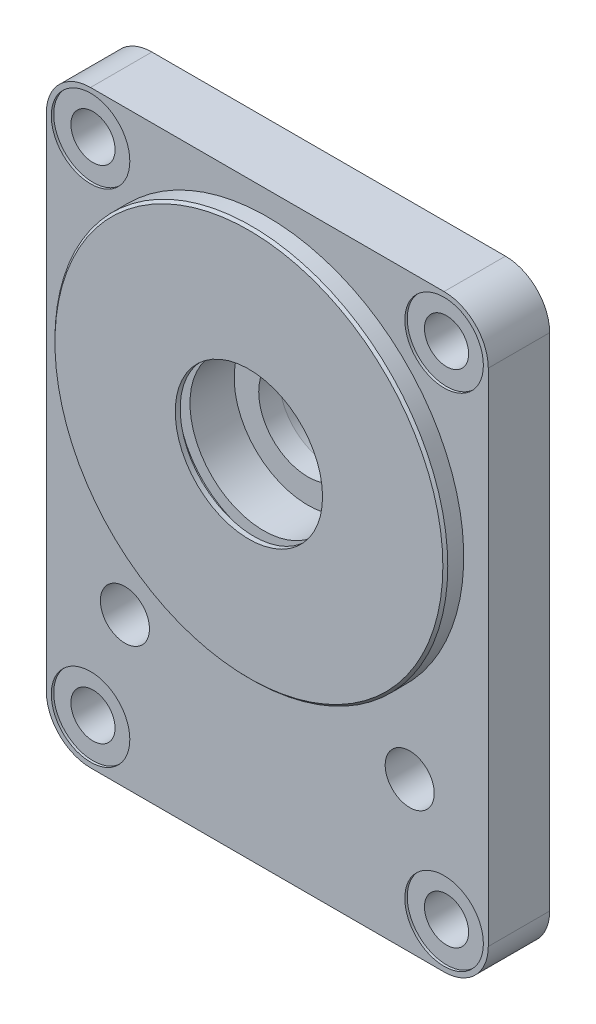
SolidWorks part; units mm, degrees
ref_plane "Front Plane" through (0, 0, 0) normal (0, 0, 1) x (1, 0, 0)
ref_plane "Top Plane" through (0, 0, 0) normal (0, 1, 0) x (1, 0, 0)
ref_plane "Right Plane" through (0, 0, 0) normal (1, 0, 0) x (0, 0, -1)
sketch "Sketch1" plane through (0, 0, 0) normal (0, 0, 1) x (1, 0, 0)
  line L1 (-36, -60) -> (36, -60)
  line L2 (-45, -51) -> (-45, 51)
  line L3 (-36, 60) -> (36, 60)
  line L4 (45, -51) -> (45, 51)
  line L6 (-45, 60) -> (-43.8588, 58.4785) construction
  arc A0 (-36, -60) -> (-45, -51) centre (-36, -51) cw
  arc A1 (36, -60) -> (45, -51) centre (36, -51) ccw
  arc A2 (36, 60) -> (45, 51) centre (36, 51) cw
  arc A3 (-45, 51) -> (-36, 60) centre (-36, 51) cw
  point P0 (0, 0)
  dimension "D3" = 9
extrude "Boss-Extrude1" add sketch "Sketch1" along normal mid plane 12.5
sketch "Sketch2" plane through (0, 0, -6.25) normal (0, 0, -1) x (-1, 0, 0)
  line L2 (42, 27.1293) -> (42, -27.1293)
  line L3 (-42, 27.1293) -> (-42, -27.1293)
  arc A0 (29.3283, 40.4951) -> (-29.3283, 40.4951) centre (0, 0) ccw
  circle A1 centre (0, 15.2) radius 10
  circle A2 centre (29, 29.5) radius 5
  circle A3 centre (29, -29.5) radius 5
  circle A4 centre (-29, -29.5) radius 5
  circle A5 centre (-29, 29.5) radius 5
  arc A6 (39.9879, 30.0161) -> (29.3283, 40.4951) centre (29, 29.5) ccw
  arc A7 (-39.9879, 30.0161) -> (-29.3283, 40.4951) centre (-29, 29.5) cw
  arc A8 (39.9879, -30.0161) -> (29.3283, -40.4951) centre (29, -29.5) cw
  arc A9 (-39.9879, -30.0161) -> (-29.3283, -40.4951) centre (-29, -29.5) ccw
  arc A10 (-39.9879, 30.0161) -> (-42, 27.1293) centre (0, 0) ccw
  arc A11 (-29.3283, -40.4951) -> (29.3283, -40.4951) centre (0, 0) ccw
  arc A12 (39.9879, -30.0161) -> (42, -27.1293) centre (0, 0) ccw
  arc A13 (42, 27.1293) -> (39.9879, 30.0161) centre (0, 0) ccw
  arc A14 (-42, -27.1293) -> (-39.9879, -30.0161) centre (0, 0) ccw
  point P10 (0, 0)
  point P15 (0, 0)
  dimension "D1" = 100
  dimension "D2" = 20
  dimension "D4" = 10
  dimension "D8" = 22
  dimension "D3" = 15.2
  dimension "D5" = 29.5
  dimension "D6" = 58
extrude "Boss-Extrude2" add sketch "Sketch2" along normal blind 3 draft 10
sketch "Sketch3" plane through (0, 0, -6.25) normal (0, 0, -1) x (-1, 0, 0)
  circle A0 centre (29, -29.5) radius 5 construction
  circle A1 centre (-29, -29.5) radius 5 construction
  circle A2 centre (29, 29.5) radius 5 construction
  circle A3 centre (-29, 29.5) radius 5 construction
  circle A4 centre (29, -29.5) radius 5
  circle A5 centre (-29, -29.5) radius 5
  circle A6 centre (29, 29.5) radius 5
  circle A7 centre (-29, 29.5) radius 5
  circle A9 centre (0, 15.2) radius 10
  circle A10 centre (0, 15.2) radius 10
  dimension "D1" = 0
extrude "Cut-Extrude1" cut sketch "Sketch3" against normal through all
sketch "Sketch5" plane through (0, 0, 6.25) normal (0, 0, 1) x (1, 0, 0)
  circle A0 centre (0, 15.2) radius 40
  dimension "D1" = 80
extrude "Boss-Extrude3" add sketch "Sketch5" along normal mid plane 7.5
sketch "Sketch6" plane through (0, 0, 10) normal (0, 0, 1) x (1, 0, 0)
  circle A0 centre (0, 15.2) radius 15
  dimension "D1" = 30
extrude "Cut-Extrude2" cut sketch "Sketch6" against normal blind 1
sketch "Sketch7" plane through (0, 0, 9) normal (0, 0, 1) x (1, 0, 0)
  circle A0 centre (0, 15.2) radius 17.5
  dimension "D1" = 35
extrude "Cut-Extrude3" cut sketch "Sketch7" against normal blind 2
sketch "Sketch8" plane through (0, 0, 7) normal (0, 0, 1) x (1, 0, 0)
  circle A0 centre (0, 15.2) radius 15
extrude "Cut-Extrude4" cut sketch "Sketch8" against normal blind 9
sketch "Sketch11" plane through (0, 0, 6.25) normal (0, 0, 1) x (1, 0, 0)
  circle A0 centre (36, 51) radius 4.5
  circle A1 centre (-36, 51) radius 4.5
  circle A2 centre (36, -51) radius 4.5
  circle A3 centre (-36, -51) radius 4.5
  point P6 (0, 0)
  point P10 (0, 0)
  dimension "D1" = 9
extrude "Cut-Extrude5" cut sketch "Sketch11" against normal through all
sketch "Sketch13" plane through (0, 0, 6.25) normal (0, 0, 1) x (1, 0, 0)
  circle A0 centre (36, 51) radius 8
  circle A1 centre (-36, 51) radius 8
  circle A2 centre (-36, -51) radius 8
  circle A3 centre (36, -51) radius 8
  dimension "D1" = 16
extrude "Cut-Extrude6" cut sketch "Sketch13" against normal blind 0.5
fillet "Chamfer1" radius 0.5 1 edges at (40, 15.2, 10) type face fillet profile chamfer first side face at (15, 15.2, 10) second side face at (40, 15.2, 10)
sketch "Sketch14" plane through (0, 0, -9.25) normal (0, 0, -1) x (-1, 0, 0)
  circle A0 centre (0, 39.5) radius 2
  circle A1 centre (0, -39.5) radius 2
  point P6 (0, 0)
  dimension "D1" = 4
  dimension "D2" = 39.5
extrude "Cut-Extrude8" cut sketch "Sketch14" against normal blind 3
chamfer "Chamfer2" distance 0.5 angle 45 2 edges at (2, -39.5, -6.25) (-2, 39.5, -6.25)
